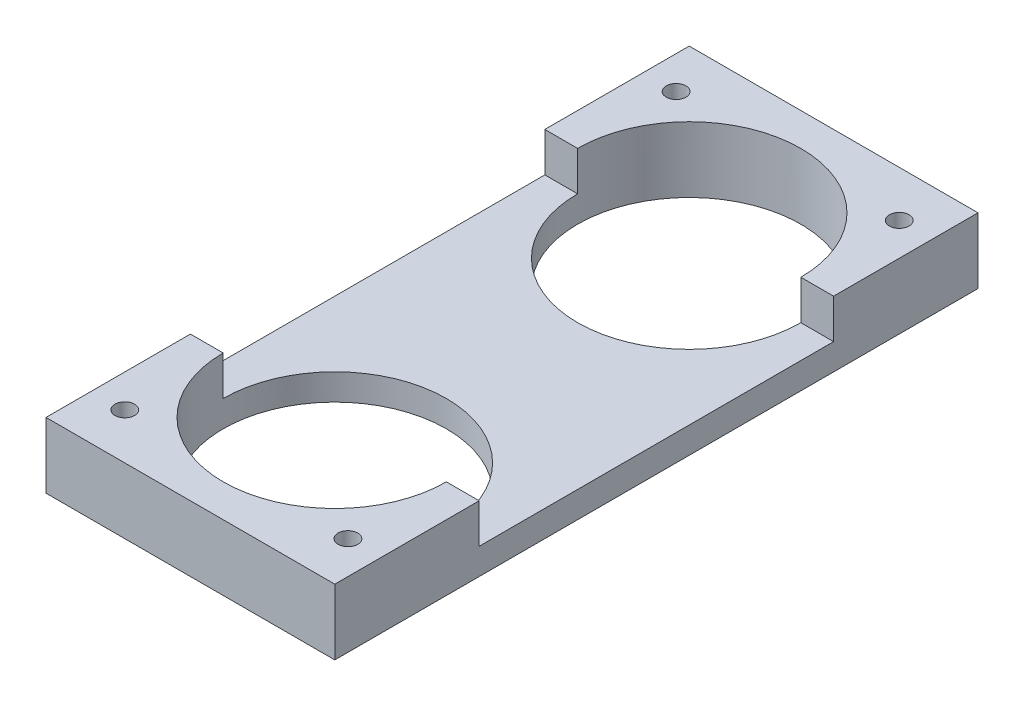
SolidWorks part; units mm, degrees
ref_plane "前视基准面" through (0, 0, 0) normal (0, 0, 1) x (1, 0, 0)
ref_plane "上视基准面" through (0, 0, 0) normal (0, 1, 0) x (1, 0, 0)
ref_plane "右视基准面" through (0, 0, 0) normal (1, 0, 0) x (0, 0, -1)
sketch "草图1" plane through (0, 0, 0) normal (0, 1, 0) x (1, 0, 0)
  line L1 (11, 24.5) -> (-11, 24.5)
  line L2 (11, 24.5) -> (11, -24.5)
  line L3 (11, -24.5) -> (-11, -24.5)
  line L4 (-11, 24.5) -> (-11, -24.5)
  line L5 (11, 24.5) -> (-11, -24.5) construction
  line L6 (11, -24.5) -> (-11, 24.5) construction
  point P0 (0, 0)
  dimension "D1" = 22
  dimension "D2" = 49
extrude "底座" add sketch "草图1" along normal blind 2
sketch "草图2" plane through (0, 2, 0) normal (0, 1, 0) x (1, 0, 0)
  line L0 (-11, 24.5) -> (-11, -24.5) construction
  line L1 (11, 13.5) -> (-11, 13.5)
  line L2 (11, 13.5) -> (11, -13.5)
  line L3 (11, -13.5) -> (-11, -13.5)
  line L4 (-11, 13.5) -> (-11, -13.5)
  line L5 (11, 13.5) -> (-11, -13.5) construction
  line L6 (11, -13.5) -> (-11, 13.5) construction
  point P0 (0, 0)
  line M2 (-11, 24.5) -> (-11, -24.5)
  line M3 (-11, -24.5) -> (11, -24.5)
  line M4 (11, -24.5) -> (11, 24.5)
  line M5 (11, 24.5) -> (-11, 24.5)
  dimension "D1" = 27
extrude "高台" add sketch "草图2" along normal blind 3 contours L3 M4 M2 M3 | L1 M4 M5 M2 region at (0, 2, -19) region at (0, 2, 19)
sketch "草图3" plane through (0, 0, 0) normal (0, -1, 0) x (1, 0, 0)
  line L0 (11, 0) -> (-11, 0)
  line L1 (-11, -24.5) -> (-11, 24.5) construction
  circle A0 centre (0, 13.5) radius 8.5
  circle A1 centre (0, -13.5) radius 8.5
  point P8 (0, 0)
  dimension "D1" = 17
  dimension "D2" = 13.5
extrude "穿孔" cut sketch "草图3" against normal through all contours A0 | A1
sketch "草图4" plane through (0, 5, 0) normal (0, 1, 0) x (1, 0, 0)
  line L0 (11, 0) -> (-11, 0)
  line L1 (-11, 13.5) -> (-11, -13.5) construction
  line L2 (0, 24.5) -> (0, -24.5)
  line L3 (-11, -24.5) -> (11, -24.5) construction
  circle A0 centre (-8.5, -21) radius 0.75
  circle A1 centre (8.5, -21) radius 0.75
  circle A2 centre (8.5, 21) radius 0.75
  circle A3 centre (-8.5, 21) radius 0.75
  point P8 (0, 0)
  point P14 (0, 0)
  dimension "D1" = 1.5
  dimension "D2" = 8.5
  dimension "D3" = 21
extrude "螺丝口" cut sketch "草图4" against normal blind 3 contours A0 | A1 | A3 | A2
